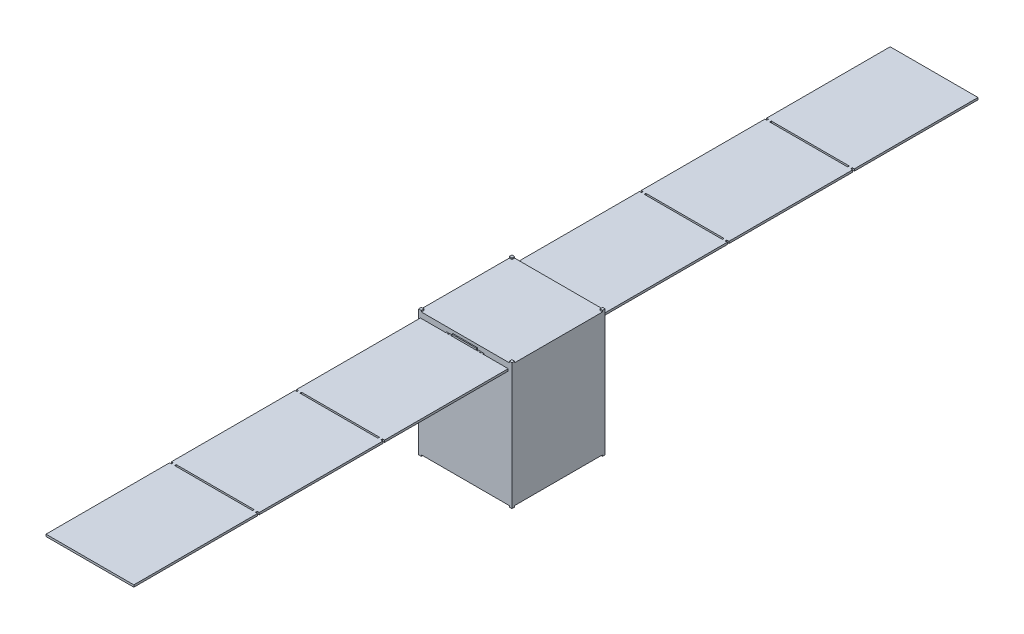
SolidWorks part; units mm, degrees
ref_plane "Piano frontale" through (0, 0, 0) normal (0, 0, 1) x (1, 0, 0)
ref_plane "Piano superiore" through (0, 0, 0) normal (0, 1, 0) x (1, 0, 0)
ref_plane "Piano destro" through (0, 0, 0) normal (1, 0, 0) x (0, 0, -1)
sketch "Schizzo2" plane through (0, 0, 0) normal (0, 1, 0) x (1, 0, 0)
  line L0 (-113.15, 106.65) -> (-113.15, -106.65)
  line L5 (-106.65, 113.15) -> (106.65, 113.15)
  line L6 (113.15, 106.65) -> (113.15, -106.65)
  line L7 (106.65, -113.15) -> (-106.65, -113.15)
  line L10 (-113.15, 106.65) -> (-106.65, 106.65)
  line L11 (-106.65, 113.15) -> (-106.65, 106.65)
  line L14 (-106.65, -113.15) -> (-106.65, -106.65)
  line L15 (-113.15, -106.65) -> (-106.65, -106.65)
  line L16 (113.15, -106.65) -> (106.65, -106.65)
  line L17 (106.65, -113.15) -> (106.65, -106.65)
  line L36 (106.65, 113.15) -> (106.65, 106.65)
  line L37 (106.65, 106.65) -> (113.15, 106.65)
extrude "Estrusione-Estrusione2" add sketch "Schizzo2" along normal blind 150 and the other way blind 150
sketch "Schizzo3" plane through (0, -150, 0) normal (0, -1, 0) x (1, 0, 0)
  line L1 (-106.65, 113.15) -> (-113.15, 113.15)
  line L2 (-106.65, 113.15) -> (-106.65, 106.65)
  line L3 (-106.65, 106.65) -> (-113.15, 106.65)
  line L4 (-113.15, 113.15) -> (-113.15, 106.65)
  line L5 (106.65, 113.15) -> (113.15, 113.15)
  line L6 (106.65, 113.15) -> (106.65, 106.65)
  line L7 (106.65, 106.65) -> (113.15, 106.65)
  line L8 (113.15, 113.15) -> (113.15, 106.65)
  line L9 (106.65, -106.65) -> (113.15, -106.65)
  line L10 (106.65, -106.65) -> (106.65, -113.15)
  line L11 (106.65, -113.15) -> (113.15, -113.15)
  line L12 (113.15, -106.65) -> (113.15, -113.15)
  line L13 (-106.65, -106.65) -> (-113.15, -106.65)
  line L14 (-106.65, -106.65) -> (-106.65, -113.15)
  line L15 (-106.65, -113.15) -> (-113.15, -113.15)
  line L16 (-113.15, -106.65) -> (-113.15, -113.15)
extrude "Estrusione-Estrusione3" add sketch "Schizzo3" along normal blind 3.3 and the other way blind 303.3
sketch "Schizzo11" plane through (0, 0, -113.15) normal (0, 0, -1) x (-1, 0, 0)
  line L0 (-106.65, 150) -> (106.65, 150) construction
  line L1 (-30, 143) -> (30, 143)
  line L2 (-30, 143) -> (-30, 139)
  line L3 (-30, 139) -> (30, 139)
  line L4 (30, 143) -> (30, 139)
  line L5 (-45, 139) -> (45, 139)
  line L6 (-45, 139) -> (-45, 132)
  line L7 (-45, 132) -> (45, 132)
  line L8 (45, 139) -> (45, 132)
  line L10 (-45, 135.5) -> (-43, 135.5)
  line L11 (-45, 135.5) -> (-45, 132)
  line L12 (-45, 132) -> (-43, 132)
  line L13 (-43, 135.5) -> (-43, 132)
  line L14 (-43, 133.75) -> (43, 133.75)
  line L15 (-43, 133.75) -> (-43, 132)
  line L16 (-43, 132) -> (43, 132)
  line L17 (0, 133.75) -> (0, 132)
  line L18 (43, 133.75) -> (43, 132)
  line L19 (45, 132) -> (43, 132)
  line L20 (43, 135.5) -> (43, 132)
  line L21 (45, 135.5) -> (43, 135.5)
  line L22 (45, 135.5) -> (45, 132)
  point P10 (0, 150)
  dimension "D1" = 7
  dimension "D2" = 4
  dimension "D3" = 60
  dimension "D4" = 30
  dimension "D5" = 0
  dimension "D6" = 90
  dimension "D7" = 45
  dimension "D8" = 7
  dimension "D9" = 2
extrude "Estrusione-Estrusione10" add sketch "Schizzo11" along normal blind 2.5 contours L1 L4 L3 L2
extrude "Estrusione-Estrusione11" add sketch "Schizzo11<5>" along normal blind 2.5 contours L21 L8 L5 L3 L6 L10 L13 L14 L20 region at (0, 136.4013, -113.15)
sketch "Schizzo11<5>" plane through (0, 0, -113.15) normal (0, 0, -1) x (-1, 0, 0) same geometry as "Schizzo11"
extrude "Estrusione-Estrusione12" add sketch "Schizzo11<8>" along normal blind 4.5 contours L18 L14 L17 L16 | L17 L14 L13 L7 | L13 L10 L6 L7 | L8 L21 L20 L18 L7 region at (44, 133.75, -113.15) region at (-44, 133.75, -113.15) region at (21.5, 132.875, -113.15) region at (-21.5, 132.875, -113.15)
sketch "Schizzo11<8>" plane through (0, 0, -113.15) normal (0, 0, -1) x (-1, 0, 0) same geometry as "Schizzo11"
sketch "Schizzo13" plane through (0, 0, -115.65) normal (0, 0, -1) x (-1, 0, 0)
  line L2 (-106.65, 138.75) -> (106.35, 138.75)
  line L3 (-106.65, 138.75) -> (-106.65, 133.75)
  line L4 (-106.65, 133.75) -> (106.35, 133.75)
  line L5 (106.35, 138.75) -> (106.35, 133.75)
  line L7 (-113.15, 153.3) -> (-113.15, -153.3) construction
  line L8 (-43, 133.75) -> (43, 133.75) construction
  dimension "D1" = 5
  dimension "D2" = 213
  dimension "D3" = 6.5
  dimension "D4" = 0
extrude "Estrusione-Estrusione13" add sketch "Schizzo13" along normal blind 300
sketch "Schizzo15" plane through (0, 0, -415.65) normal (0, 0, -1) x (-1, 0, 0)
  line L0 (106.35, 138.75) -> (-106.65, 138.75) construction
  line L1 (-101.65, 138.75) -> (-94.65, 138.75)
  line L2 (-101.65, 138.75) -> (-101.65, 133.75)
  line L3 (-101.65, 133.75) -> (-94.65, 133.75)
  line L4 (-94.65, 138.75) -> (-94.65, 133.75)
  line L5 (-106.65, 133.75) -> (106.35, 133.75) construction
  line L6 (-106.65, 138.75) -> (-106.65, 133.75) construction
  line L9 (101.65, 133.75) -> (94.65, 133.75)
  line L10 (94.65, 138.75) -> (94.65, 133.75)
  line L11 (101.65, 138.75) -> (94.65, 138.75)
  line L12 (101.65, 138.75) -> (101.65, 133.75)
  dimension "D1" = 5
  dimension "D2" = 7
extrude "Estrusione-Estrusione14" add sketch "Schizzo15" along normal blind 4
sketch "Schizzo16" plane through (0, 0, -419.65) normal (0, 0, -1) x (-1, 0, 0)
  line L1 (-106.65, 138.75) -> (106.35, 138.75)
  line L2 (-106.65, 138.75) -> (-106.65, 133.75)
  line L3 (-106.65, 133.75) -> (106.35, 133.75)
  line L4 (106.35, 138.75) -> (106.35, 133.75)
extrude "Estrusione-Estrusione15" add sketch "Schizzo16" along normal blind 300
pattern_linear "Ripetizione a L2" count 2 spacing 304 along (0, 0, -1) of "Estrusione-Estrusione15", "Estrusione-Estrusione14"
sketch3d "Schizzo3D1" plane through (0, 0, 0) normal (0, 0, 1) x (1, 0, 0)
mirror "Specchia2" about plane through (0, 0, 0) normal (0, 0, 1) of "Estrusione-Estrusione10", "Estrusione-Estrusione11", "Estrusione-Estrusione12", "Estrusione-Estrusione13", "Estrusione-Estrusione14", "Estrusione-Estrusione15", "Ripetizione a L2"
